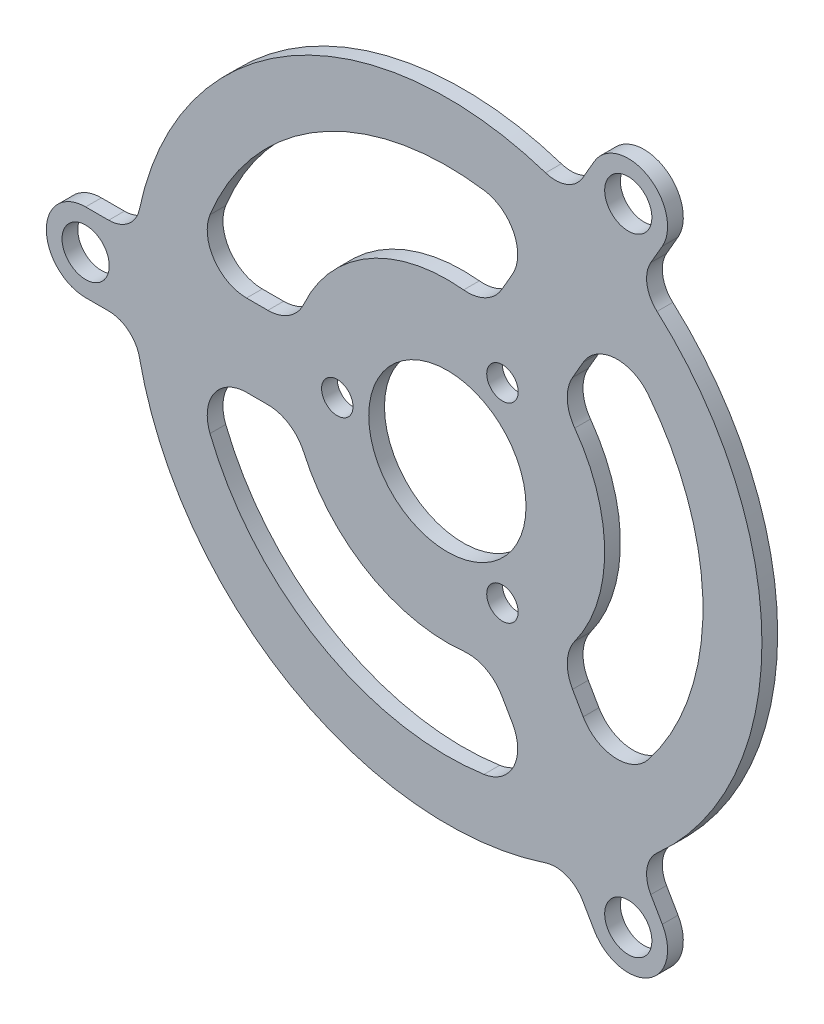
SolidWorks part; units mm, degrees
material "1060 Alloy"
ref_plane "Front Plane" through (0, 0, 0) normal (0, 0, 1) x (1, 0, 0)
ref_plane "Top Plane" through (0, 0, 0) normal (0, 1, 0) x (1, 0, 0)
ref_plane "Right Plane" through (0, 0, 0) normal (1, 0, 0) x (0, 0, -1)
sketch "Sketch1" plane through (0, 0, 0) normal (0, 0, 1) x (1, 0, 0)
  circle A0 centre (0, 0) radius 40
  dimension "D1" = 80
extrude "Boss-Extrude1" add sketch "Sketch1" along normal blind 2
ref_axis "Axis1" through (0, 0, 2) along (0, 0, -1)
sketch "Sketch4" plane through (0, 0, 0) normal (0, 0, -1) x (-1, 0, 0)
  line L0 (0, 0) -> (-40, 0) construction
  line L1 (0, 0) -> (20, 34.641) construction
  line L2 (0, 0) -> (-20, 34.641) construction
  line L3 (-20, 34.641) -> (-23, 39.8372) construction
  line L4 (-18.6699, 42.3372) -> (-15.513, 36.8693)
  line L5 (-27.3301, 37.3372) -> (-24.1733, 31.8693)
  line L6 (-27.3301, 37.3372) -> (-18.6699, 42.3372)
  line L7 (-24.1733, 31.8693) -> (-15.513, 36.8693)
  circle A0 centre (0, 0) radius 40 construction
  circle A1 centre (-23, 39.8372) radius 3
  arc A2 (-18.6699, 42.3372) -> (-27.3301, 37.3372) centre (-23, 39.8372) ccw
  circle M29 centre (0, 0) radius 40
  dimension "D3" = 6
  dimension "D5" = 2
  dimension "D1" = 120
  dimension "D2" = 60
  dimension "D4" = 6
extrude "Boss-Extrude3" add sketch "Sketch4" against normal blind 2 contours A1 L6 L5 L4 M29 | L6 A2 A1 region at (21.2054, 36.7287, 0) region at (19.5958, 41.9408, 0)
fillet "Fillet2" radius 4 2 edges at (24.1733, 31.8693, 1) (15.513, 36.8693, 1)
pattern_circular "CirPattern2" count 3 over 360 about axis through (0, 0, 2) along (0, 0, -1) of "Boss-Extrude3", "Fillet2"
sketch "Sketch5" plane through (0, 0, 0) normal (0, 0, -1) x (-1, 0, 0)
  circle A0 centre (0, 0) radius 10
  dimension "D1" = 20
extrude "Cut-Extrude1" cut sketch "Sketch5" against normal blind 8
sketch "Sketch6" plane through (0, 0, 0) normal (0, 0, -1) x (-1, 0, 0)
  line L0 (0, 0) -> (20.4476, 0) construction
  line L1 (0, 0) -> (-7, 12.1244) construction
  circle A0 centre (-7, 12.1244) radius 2
  dimension "D3" = 4
  dimension "D1" = 120
  dimension "D2" = 14
extrude "Cut-Extrude2" cut sketch "Sketch6" against normal blind 8
pattern_circular "CirPattern3" count 3 over 360 about axis through (0, 0, 2) along (0, 0, -1) of "Cut-Extrude2"
sketch "Sketch7" plane through (0, 0, 0) normal (0, 0, -1) x (-1, 0, 0)
  line L0 (0, 0) -> (54.9623, 0) construction
  line L1 (3, 5.1962) -> (32.0819, 5.1962)
  line L2 (-24.1148, 41.7681) -> (0, 0) construction
  line L3 (3, 5.1962) -> (-11.541, 30.3818)
  line L4 (0, 0) -> (3, 5.1962) construction
  circle A0 centre (0, 0) radius 20
  circle A1 centre (0, 0) radius 32.5
  circle A2 centre (0, 0) radius 6
  dimension "D2" = 12
  dimension "D4" = 40
  dimension "D5" = 65
  dimension "D1" = 120
  dimension "D3" = 60
extrude "Cut-Extrude3" cut sketch "Sketch7" against normal blind 15 contours L1 A1 L3 A0 region at (-11.8621, 20.5457, 0)
fillet "Fillet3" radius 5 4 edges at (-32.0819, 5.1962, 1) (-19.3132, 5.1962, 1) (5.1566, 19.3238, 1) (11.541, 30.3818, 1)
pattern_circular "CirPattern4" count 3 over 360 about axis through (0, 0, 2) along (0, 0, -1) of "Cut-Extrude3", "Fillet3" reverse direction yes
